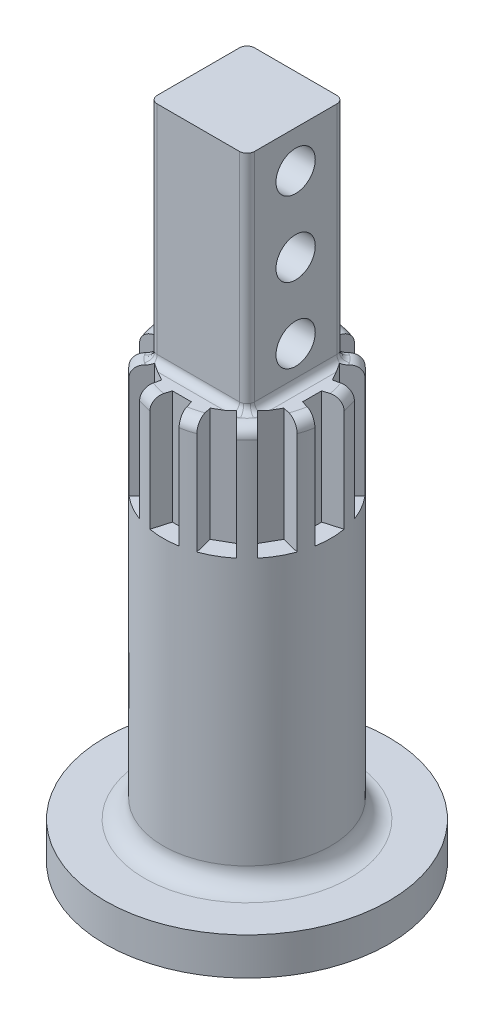
SolidWorks part; units mm, degrees
ref_plane "Front Plane" through (0, 0, 0) normal (0, 0, 1) x (1, 0, 0)
ref_plane "Top Plane" through (0, 0, 0) normal (0, 1, 0) x (1, 0, 0)
ref_plane "Right Plane" through (0, 0, 0) normal (1, 0, 0) x (0, 0, -1)
sketch "Sketch1" plane through (0, 0, 0) normal (0, 1, 0) x (1, 0, 0)
  circle A0 centre (0, 0) radius 37.9
extrude "Boss-Extrude1" add sketch "Sketch1" along normal blind 10
sketch "Sketch2" plane through (0, 10, 0) normal (0, 1, 0) x (1, 0, 0)
  circle A0 centre (0, 0) radius 22.4
extrude "Boss-Extrude2" add sketch "Sketch2" along normal blind 101.6
fillet "Fillet1" radius 5 1 edges at (0, 10, 22.4)
sketch "Sketch8" plane through (0, 111.6, 0) normal (0, 1, 0) x (1, 0, 0)
  line L0 (0, 22.4) -> (-4, 22.4)
  line L1 (0, 22.4) -> (4, 22.4)
  line L8 (-2.5662, 17.4) -> (2.5662, 17.4)
  line L9 (2.5662, 17.4) -> (4, 22.4)
  line L10 (-2.5662, 17.4) -> (-4, 22.4)
  circle A1 centre (0, 0) radius 22.4 construction
  dimension "D1" = 4
  dimension "D2" = 5
  dimension "D3" = 4
extrude "Cut-Extrude3" cut sketch "Sketch8" against normal blind 25.4 and the other way blind 5
pattern_circular "CirPattern1" count 12 over 360 about axis through (0, 111.6, 0) along (0, 1, 0) of "Cut-Extrude3"
sketch "Sketch5" plane through (0, 111.6, 0) normal (0, 1, 0) x (1, 0, 0)
  circle A0 centre (0, 0) radius 22.4
extrude "Boss-Extrude3" add sketch "Sketch5" along normal blind 5
sketch "Sketch6" plane through (0, 116.6, 0) normal (0, 1, 0) x (1, 0, 0)
  line L0 (0, 0) -> (13, 0)
  line L1 (0, 0) -> (-13, 0)
  line L2 (-13, 0) -> (-13, 13)
  line L3 (-13, 0) -> (-13, -13)
  line L4 (-13, 13) -> (13, 13)
  line L5 (13, 13) -> (13, -13)
  line L6 (13, -13) -> (-13, -13)
  dimension "D1" = 13
  dimension "D2" = 13
  dimension "D3" = 13
  dimension "D4" = 13
extrude "Boss-Extrude4" add sketch "Sketch6" along normal blind 60 contours L5 L4 L2 L1 L0 | L6 L5 L0 L1 L3 region at (0, 116.6, -6.5) region at (0, 116.6, 6.5)
sketch "Sketch7" plane through (13, 0, 0) normal (1, 0, 0) x (0, 0, -1)
  line L7 (0, 176.6) -> (0, 116.6)
  line L9 (13, 176.6) -> (-13, 176.6) construction
  line L10 (22.4, 116.6) -> (-22.4, 116.6) construction
  line L11 (13, 116.6) -> (-13, 116.6) construction
  circle A6 centre (0, 146.6) radius 5.25
  circle A7 centre (0, 166.6) radius 5.25
  circle A8 centre (0, 126.6) radius 5.25
  dimension "D2" = 10
  dimension "D1" = 10
extrude "Cut-Extrude2" cut sketch "Sketch7" against normal blind 46 contours L7 A7 | L7 A7 | L7 A6 | L7 A6 | L7 A8 | L7 A8 region at (13, 166.6, -2.2282) region at (13, 126.6, -2.2282) region at (13, 126.6, 2.2282) region at (13, 146.6, -2.2282) region at (13, 146.6, 2.2282) region at (13, 166.6, 2.2282)
extrude "Cut-Extrude4" cut sketch "Sketch8<2>" along normal blind 25.4
sketch "Sketch8<2>" plane through (0, 111.6, 0) normal (0, 1, 0) x (1, 0, 0) same geometry as "Sketch8"
pattern_circular "CirPattern2" count 12 over 360 about axis through (0, 116.6, 0) along (0, 1, 0) of "Cut-Extrude4"
fillet "Fillet3" radius 3 12 edges at (-5.7975, 116.6, -21.6367) (5.7975, 116.6, -21.6367) (-21.6367, 116.6, -5.7975) (-21.6367, 116.6, 5.7975) (-15.8392, 116.6, 15.8392) (-5.7975, 116.6, 21.6367) (5.7975, 116.6, 21.6367) (15.8392, 116.6, 15.8392) (21.6367, 116.6, 5.7975) (21.6367, 116.6, -5.7975) (15.8392, 116.6, -15.8392) (-15.8392, 116.6, -15.8392)
fillet "Fillet4" radius 2 4 edges at (-13, 146.6, -13) (13, 146.6, -13) (13, 146.6, 13) (-13, 146.6, 13)
fillet "Fillet5" radius 2 8 edges at (-12.4142, 116.6, -12.4142) (-12.4142, 116.6, 12.4142) (12.4142, 116.6, 12.4142) (12.4142, 116.6, -12.4142) (13, 116.6, 0) (0, 116.6, 13) (-13, 116.6, 0) (0, 116.6, -13)
